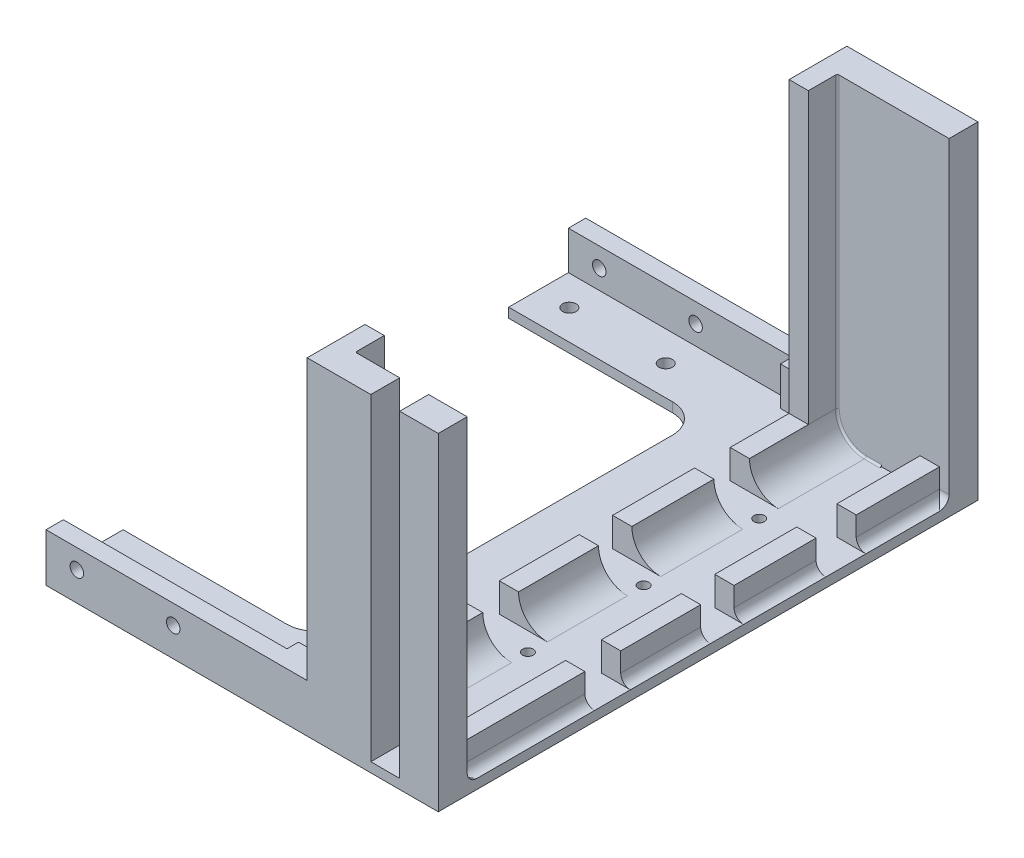
SolidWorks part; units mm, degrees
ref_plane "Front Plane" through (0, 0, 0) normal (0, 0, 1) x (1, 0, 0)
ref_plane "Top Plane" through (0, 0, 0) normal (0, 1, 0) x (1, 0, 0)
ref_plane "Right Plane" through (0, 0, 0) normal (1, 0, 0) x (0, 0, -1)
sketch "profile" plane through (0, 0, 0) normal (0, 0, 1) x (1, 0, 0)
  line L0 (11.8803, 7.4874) -> (14.5, 7.4874)
  line L1 (-5.5, 6.9749) -> (-7.8749, 4.6)
  line L2 (-7.8749, 4.6) -> (-12.1251, 4.6)
  line L3 (-12.1251, 4.6) -> (-14.5, 6.9749)
  line L4 (-8.1197, 7.4874) -> (-5.5, 7.4874)
  line L5 (-14.5, 6.9749) -> (-15.0126, 7.4874)
  line L6 (14.5, 6.9749) -> (12.1251, 4.6)
  line L7 (12.1251, 4.6) -> (7.8749, 4.6)
  line L8 (7.8749, 4.6) -> (5.5, 6.9749)
  line L9 (-14.7464, 10.3536) -> (-5.2536, 10.3536)
  line L10 (-14.5, 7.4874) -> (-11.8803, 7.4874)
  line L11 (5.5, 7.4874) -> (8.5334, 7.4874)
  line L12 (5.6673, 10.3536) -> (14.7464, 10.3536)
  line L13 (-15.0126, 7.4874) -> (-14.5, 7.4874)
  line L14 (-5.5, 6.9749) -> (-4.9874, 7.4874)
  line L15 (-4.9874, 7.4874) -> (-5.5, 7.4874)
  line L16 (5.5, 6.9749) -> (4.9874, 7.4874)
  line L17 (4.9874, 7.4874) -> (5.5, 7.4874)
  line L18 (14.5, 6.9749) -> (15.0126, 7.4874)
  line L19 (15.0126, 7.4874) -> (14.5, 7.4874)
  line L20 (-12.7464, 8.3536) -> (-14.7464, 10.3536)
  line L21 (-5.2536, 10.3536) -> (-7.2536, 8.3536)
  line L22 (7.6673, 8.3536) -> (5.6673, 10.3536)
  line L23 (14.7464, 10.3536) -> (12.7464, 8.3536)
  line L24 (-12.7464, 8.3536) -> (-11.8803, 7.4874)
  line L25 (-7.2536, 8.3536) -> (-8.1197, 7.4874)
  line L26 (7.6673, 8.3536) -> (8.5334, 7.4874)
  line L27 (12.7464, 8.3536) -> (11.8803, 7.4874)
  line L28 (-14.7464, 10.3536) -> (-20, 10.3536)
  line L29 (-20, 10.3536) -> (-20, 15.3536)
  line L30 (-20, 15.3536) -> (20, 15.3536)
  line L31 (20, 15.3536) -> (20, 10.3536)
  line L32 (20, 10.3536) -> (14.7464, 10.3536)
  line L33 (-5.2536, 10.3536) -> (5.6673, 10.3536)
  point P0 (-10, 4.6)
  point P1 (10, 4.6)
  dimension "D1" = 4.2503
  dimension "D2" = 5.7536
  dimension "D3" = 15.7497
  dimension "D4" = 20
  dimension "D5" = 5
extrude "Boss-Extrude1" add sketch "profile" along normal blind 250 contours L9 L33 L12 L32 L31 L30 L29 L28 region at (0, 12.8536, 0)
extrude "Boss-Extrude2" add sketch "Sketch1<3>" along normal blind 50 separate body contours L25 L21 L9 L20 L24 L10 L13 L5 L3 L2 L1 L14 L15 L4 | L27 L23 L12 L22 L26 L11 L17 L16 L8 L7 L6 L18 L19 L0 region at (10.0959, 7.5838, 0) region at (-10, 7.6238, 0)
sketch "Sketch1<3>" plane through (0, 0, 0) normal (0, 0, 1) x (1, 0, 0) same geometry as "profile"
pattern_linear "LPattern1" count 4 spacing 60 along (0, 0, 1) of "Boss-Extrude2"
sketch "Sketch2" plane through (0, 10.3536, 0) normal (0, -1, 0) x (1, 0, 0)
  line L0 (10, 250) -> (10, 0) construction
  line L1 (-20, 250) -> (20, 250) construction
  line L2 (12.1251, 0) -> (7.8749, 0) construction
  line L3 (-10, 230) -> (-10, 0) construction
  line L4 (-7.8749, 230) -> (-12.1251, 230) construction
  line L5 (-7.8749, 0) -> (-12.1251, 0) construction
  line L6 (-7.8749, 180) -> (-7.8749, 170) construction
  line L7 (-7.8749, 180) -> (-12.1251, 180) construction
  circle A0 centre (-10, 175) radius 2.75
  circle A1 centre (10, 175) radius 2.75
  circle A2 centre (-10, 115) radius 2.75
  circle A3 centre (10, 115) radius 2.75
  circle A4 centre (-10, 55) radius 2.75
  circle A5 centre (10, 55) radius 2.75
  point P21 (-7.8749, 175)
  dimension "D1" = 5.5
  dimension "D2" = 3
extrude "Cut-Extrude1" cut sketch "Sketch2" against normal through all
sketch "upper_acrylic_supp" plane through (0, 15.3536, 0) normal (0, 1, 0) x (1, 0, 0)
  line L0 (-20, 0) -> (20, 0) construction
  line L1 (-20, -250) -> (-34.5, -250) construction
  line L2 (-20, -250) -> (-20, 0) construction
  line L3 (-20, 0) -> (-34.5, 0) construction
  line L4 (-34.5, -250) -> (-34.5, 0) construction
  line L6 (-34.5, -250) -> (-24.5, -250)
  line L7 (-34.5, -250) -> (-34.5, -183.9264)
  line L8 (-34.5, -183.9264) -> (-24.5, -183.9264)
  line L9 (-24.5, -250) -> (-24.5, -183.9264)
  line L10 (-34.5, -165.3527) -> (-24.5, -165.3527)
  line L11 (-34.5, -165.3527) -> (-34.5, -123.8775)
  line L12 (-34.5, -123.8775) -> (-24.5, -123.8775)
  line L13 (-24.5, -165.3527) -> (-24.5, -123.8775)
  line L14 (-34.5, -106.5661) -> (-24.5, -106.5661)
  line L15 (-34.5, -106.5661) -> (-34.5, -64.0089)
  line L16 (-34.5, -64.0089) -> (-24.5, -64.0089)
  line L17 (-24.5, -106.5661) -> (-24.5, -64.0089)
  line L18 (-34.5, -45.5583) -> (-24.5, -45.5583)
  line L19 (-34.5, -45.5583) -> (-34.5, 0)
  line L20 (-34.5, 0) -> (-24.5, 0)
  line L21 (-24.5, -45.5583) -> (-24.5, 0)
  line L22 (-20, -250) -> (-40, -250)
  line L23 (-20, -250) -> (-20, 0)
  line L24 (-20, 0) -> (-40, 0)
  line L25 (-40, -250) -> (-40, 0)
  line M21 (-20, 0) -> (-20, -250)
  dimension "D1" = 5.5
  dimension "D2" = 10
  dimension "D3" = 20
extrude "Boss-Extrude3" add sketch "upper_acrylic_supp" against normal blind 5 contours L25 L22 L24 L21 L18 L19 L17 L14 L15 L16 L13 L10 L11 L12 L9 L6 L7 L8 M21 | L14 L17 L16 L15 | L10 L13 L12 L11 | L6 L9 L8 L7 | L18 L21 L20 L19 region at (-29.5, 15.3536, 216.9632) region at (-30.3215, 15.3536, 123.2164) region at (-29.5, 15.3536, 22.7792) region at (-29.5, 15.3536, 144.6151) region at (-29.5, 15.3536, 85.2875)
extrude "Boss-Extrude4" add sketch "upper_acrylic_supp<3>" along normal blind 15 contours L6 L9 L8 L7 | L10 L13 L12 L11 | L14 L17 L16 L15 | L18 L21 L20 L19 region at (-29.5, 15.3536, 216.9632) region at (-29.5, 15.3536, 22.7792) region at (-29.5, 15.3536, 144.6151) region at (-29.5, 15.3536, 85.2875)
sketch "upper_acrylic_supp<3>" plane through (0, 15.3536, 0) normal (0, 1, 0) x (1, 0, 0) same geometry as "upper_acrylic_supp"
fillet "Fillet1" radius 15 4 edges at (-24.5, 15.3536, 22.7792) (-24.5, 15.3536, 85.2875) (-24.5, 15.3536, 144.6151) (-24.5, 15.3536, 216.9632)
sketch "Sketch4" plane through (0, 15.3536, 0) normal (0, 1, 0) x (1, 0, 0)
  line L0 (20, -250) -> (20, 0) construction
  line L1 (-40, -250) -> (20, -250)
  line L2 (-40, -250) -> (-40, -265)
  line L3 (-40, -265) -> (20, -265)
  line L4 (20, -250) -> (20, -265)
  line L5 (-40, 0) -> (20, 0)
  line L6 (-40, 0) -> (-40, 15)
  line L7 (-40, 15) -> (20, 15)
  line L8 (20, 0) -> (20, 15)
  line L10 (-34.5, -265) -> (-34.5, 15) construction
  dimension "D1" = 15
  dimension "D2" = 15
extrude "Boss-Extrude5" add sketch "Sketch4" along normal mid plane 10
extrude "Boss-Extrude6" add sketch "Sketch4<3>" along normal blind 60
sketch "Sketch4<3>" plane through (0, 15.3536, 0) normal (0, 1, 0) x (1, 0, 0) same geometry as "Sketch4"
sketch "Sketch5" plane through (0, 0, 250) normal (0, 0, -1) x (-1, 0, 0)
  line L0 (-20, 75.3536) -> (40, 75.3536) construction
  line L1 (40, 15.3536) -> (34.5, 15.3536)
  line L2 (40, 15.3536) -> (40, 75.3536)
  line L3 (40, 75.3536) -> (34.5, 75.3536)
  line L4 (34.5, 15.3536) -> (34.5, 75.3536)
  line L6 (34.5, 15.3536) -> (24.5, 15.3536)
  line L7 (34.5, 15.3536) -> (34.5, 75.3536)
  line L8 (34.5, 75.3536) -> (24.5, 75.3536)
  line L9 (24.5, 15.3536) -> (24.5, 75.3536)
  line M5 (40, 75.3536) -> (-20, 75.3536)
  line M9 (24.5, 30.3536) -> (34.5, 30.3536)
  dimension "D1" = 5.5
  dimension "D2" = 10
extrude "Boss-Extrude7" add sketch "Sketch5" along normal blind 15 contours L9 L4 M9 M5 region at (-29.5, 52.8536, 250)
extrude "Boss-Extrude8" add sketch "Sketch5<3>" against normal blind 15 from surface contours L9 L4 M9 M5 region at (-29.5, 52.8536, 250) starting at face at (-18.2633, 33.7152, 0)
sketch "Sketch5<3>" plane through (0, 0, 250) normal (0, 0, -1) x (-1, 0, 0) same geometry as "Sketch5"
fillet "Fillet2" radius 1 6 edges at (5.25, 15.3536, 0) (-20.1066, 19.747, 0) (5.25, 15.3536, 250) (-20.1066, 19.747, 250) (-24.5, 52.8536, 0) (-24.5, 52.8536, 250)
sketch "Sketch6" plane through (-40, 0, 0) normal (-1, 0, 0) x (0, 0, 1)
  line L1 (250, 15.3536) -> (256, 15.3536)
  line L2 (250, 15.3536) -> (250, 75.3536)
  line L3 (250, 75.3536) -> (256, 75.3536)
  line L4 (256, 15.3536) -> (256, 75.3536)
  line L6 (0, 15.3536) -> (-6, 15.3536)
  line L7 (0, 15.3536) -> (0, 75.3536)
  line L8 (0, 75.3536) -> (-6, 75.3536)
  line L9 (-6, 15.3536) -> (-6, 75.3536)
  dimension "D1" = 6
  dimension "D2" = 6
extrude "Cut-Extrude2" cut sketch "Sketch6" against normal blind 6
sketch "Sketch7" plane through (-40, 0, 0) normal (-1, 0, 0) x (0, 0, 1)
  line L8 (265, 75.3536) -> (256, 75.3536)
  line L9 (256, 75.3536) -> (256, 15.3536)
  line L10 (256, 15.3536) -> (-6, 15.3536)
  line L11 (-6, 15.3536) -> (-6, 75.3536)
  line L12 (-6, 75.3536) -> (-15, 75.3536)
  line L13 (-15, 75.3536) -> (-15, 10.3536)
  line L14 (-15, 10.3536) -> (265, 10.3536)
  line L15 (265, 10.3536) -> (265, 75.3536)
  line L16 (265, 75.3536) -> (256, 75.3536)
  line L17 (256, 75.3536) -> (256, 15.3536)
  line L18 (256, 15.3536) -> (-6, 15.3536)
  line L19 (-6, 15.3536) -> (-6, 75.3536)
  line L20 (-6, 75.3536) -> (-15, 75.3536)
  line L21 (-15, 75.3536) -> (-15, 10.3536)
  line L22 (-15, 10.3536) -> (265, 10.3536)
  line L23 (265, 10.3536) -> (265, 75.3536)
  dimension "D1" = 0
extrude "Boss-Extrude9" add sketch "Sketch7" along normal blind 30
sketch "Sketch8" plane through (-70, 0, 0) normal (-1, 0, 0) x (0, 0, 1)
  line L0 (-15, 10.3536) -> (265, 10.3536) construction
  line L1 (-44.3745, 35.3536) -> (289.2282, 35.3536)
  line L2 (-44.3745, 35.3536) -> (-44.3745, 94.3849)
  line L3 (-44.3745, 94.3849) -> (289.2282, 94.3849)
  line L4 (289.2282, 35.3536) -> (289.2282, 94.3849)
  dimension "D1" = 25
extrude "Cut-Extrude3" cut sketch "Sketch8" against normal blind 150
sketch "Sketch9" plane through (-34, 0, 0) normal (-1, 0, 0) x (0, 0, 1)
  line L4 (256, 15.3536) -> (256, 35.3536)
  line L5 (256, 35.3536) -> (250, 35.3536)
  line L6 (250, 35.3536) -> (250, 15.3536)
  line L7 (250, 15.3536) -> (256, 15.3536)
  line L8 (256, 15.3536) -> (256, 35.3536)
  line L9 (256, 35.3536) -> (250, 35.3536)
  line L10 (250, 35.3536) -> (250, 15.3536)
  line L11 (250, 15.3536) -> (256, 15.3536)
  line L12 (0, 35.3536) -> (-6, 35.3536)
  line L13 (-6, 35.3536) -> (-6, 15.3536)
  line L14 (-6, 15.3536) -> (0, 15.3536)
  line L15 (0, 15.3536) -> (0, 35.3536)
  line L16 (0, 35.3536) -> (-6, 35.3536)
  line L17 (-6, 35.3536) -> (-6, 15.3536)
  line L18 (-6, 15.3536) -> (0, 15.3536)
  line L19 (0, 15.3536) -> (0, 35.3536)
  dimension "D1" = 0
  dimension "D2" = 0
extrude "cloth_escape_gap" add sketch "Sketch9" along normal blind 20
sketch "Sketch11" plane through (-70, 0, 0) normal (-1, 0, 0) x (0, 0, 1)
  line L0 (256, 35.3536) -> (256, 15.3536) construction
  line L1 (-15, 35.3536) -> (-6, 35.3536)
  line L2 (-15, 35.3536) -> (-15, 15.3536)
  line L3 (-15, 15.3536) -> (-6, 15.3536)
  line L4 (-6, 35.3536) -> (-6, 15.3536)
  line L5 (265, 35.3536) -> (256, 35.3536)
  line L6 (265, 35.3536) -> (265, 15.3536)
  line L7 (265, 15.3536) -> (256, 15.3536)
  line L8 (256, 35.3536) -> (256, 15.3536)
  line L9 (256, 15.3536) -> (256, 35.3536) construction
extrude "Boss-Extrude11" add sketch "Sketch11" along normal blind 100
sketch "Sketch12" plane through (0, 10.3536, 0) normal (0, -1, 0) x (1, 0, 0)
  line L0 (-70, -15) -> (-170, -10.5)
  line L1 (-170, -15) -> (-170, -6) construction
  line L2 (-170, -10.5) -> (-170, -15)
  line L3 (-170, -15) -> (-70, -15) construction
  line L4 (-170, -15) -> (-70, -15)
  line L5 (-70, 265) -> (-170, 260.5)
  line L6 (-170, 256) -> (-170, 265) construction
  line L7 (-170, 260.5) -> (-170, 265)
  line L8 (-170, 265) -> (-70, 265)
extrude "Cut-Extrude4" cut sketch "Sketch12" against normal blind 68 contours L8 L7 L5 | L0 L2 L4 region at (-136.6667, 10.3536, 263.5)
sketch "Sketch13" plane through (-70, 0, 0) normal (-1, 0, 0) x (0, 0, 1)
  line L0 (256, 15.3536) -> (265, 15.3536) construction
  line L1 (-15, 10.3536) -> (25, 10.3536)
  line L2 (-15, 10.3536) -> (-15, 15.3536)
  line L3 (-15, 15.3536) -> (25, 15.3536)
  line L4 (25, 10.3536) -> (25, 15.3536)
  line L5 (265, 10.3536) -> (225, 10.3536)
  line L6 (265, 10.3536) -> (265, 15.3536)
  line L7 (265, 15.3536) -> (225, 15.3536)
  line L8 (225, 10.3536) -> (225, 15.3536)
  line L9 (256, 15.3536) -> (-6, 15.3536) construction
  dimension "D1" = 40
  dimension "D2" = 40
extrude "Boss-Extrude13" add sketch "Sketch13" along normal blind 100
sketch "Sketch14" plane through (0, 15.3536, 0) normal (0, 1, 0) x (1, 0, 0)
  line L3 (-70, -265) -> (-170, -260.5)
  line L4 (-170, -260.5) -> (-170, -265)
  line L5 (-170, -265) -> (-70, -265)
  line L6 (-70, -265) -> (-170, -260.5)
  line L7 (-170, -260.5) -> (-170, -265)
  line L8 (-170, -265) -> (-70, -265)
  line L9 (-170, 15) -> (-170, 10.5)
  line L10 (-170, 10.5) -> (-70, 15)
  line L11 (-70, 15) -> (-170, 15)
  line L12 (-170, 15) -> (-170, 10.5)
  line L13 (-170, 10.5) -> (-70, 15)
  line L14 (-70, 15) -> (-170, 15)
  dimension "D1" = 0
  dimension "D2" = 0
extrude "Cut-Extrude5" cut sketch "Sketch14" against normal blind 100
fillet "Fillet3" radius 15 2 edges at (-70, 12.8536, 25) (-70, 12.8536, 225)
sketch "Sketch16" plane through (0, 15.3536, 0) normal (0, 1, 0) x (1, 0, 0)
  line L0 (20, -1) -> (-9.5, -1) construction
  line L1 (-34.5, -235) -> (18.5, -235) construction
  line L2 (-34.5, -235) -> (-34.5, -1) construction
  line L3 (-34.5, -1) -> (18.5, -1) construction
  line L4 (18.5, -235) -> (18.5, -1) construction
  line L5 (20, -265) -> (-70, -265) construction
  line L6 (18.5, -265) -> (33.5, -265)
  line L7 (18.5, -265) -> (18.5, 15)
  line L8 (18.5, 15) -> (33.5, 15)
  line L9 (33.5, -265) -> (33.5, 15)
  line L10 (-70, 15) -> (20, 15) construction
  line L11 (18.5, -250) -> (33.5, -250)
  line L12 (18.5, 0) -> (33.5, 0)
  line L13 (-23.5, -250) -> (20, -250) construction
  line L14 (-9.5, 0) -> (20, 0) construction
  line L15 (18.5, -250) -> (28.5, -250)
  line L16 (28.5, -250) -> (28.5, -183.9264)
  line L17 (28.5, 0) -> (18.5, 0)
  line L18 (18.5, -183.9264) -> (28.5, -183.9264)
  line L19 (18.5, -165.3527) -> (28.5, -165.3527)
  line L20 (18.5, -123.8775) -> (28.5, -123.8775)
  line L21 (18.5, -106.5661) -> (28.5, -106.5661)
  line L22 (18.5, -64.0089) -> (28.5, -64.0089)
  line L23 (18.5, -43.1778) -> (28.5, -43.1778)
  line L24 (-34.5, -165.3527) -> (-9.5, -165.3527) construction
  line L25 (-34.5, -183.9264) -> (-9.5, -183.9264) construction
  line L26 (-34.5, -106.5661) -> (-9.5, -106.5661) construction
  line L27 (-34.5, -123.8775) -> (-9.5, -123.8775) construction
  line L28 (-9.5, -64.0089) -> (-24.5, -64.0089) construction
  line L30 (28.5, -165.3527) -> (28.5, -123.8775)
  line L31 (28.5, -106.5661) -> (28.5, -64.0089)
  line L32 (28.5, -43.1778) -> (28.5, 0)
  line M38 (-9.5, -249) -> (20, -249)
  line M39 (20, -249) -> (20, -1)
  line M40 (20, -1) -> (-9.5, -1)
  dimension "D1" = 53
  dimension "D2" = 15
  dimension "D3" = 10
extrude "Boss-Extrude14" add sketch "Sketch16" along direction (0, -1, 0) on the side of the normal up to surface (20 mm away) from surface contours L7 L12 L9 L8 | L11 L7 L6 L9 region at (26, 15.3536, 257.5) region at (26, 15.3536, -7.5) up to face at (-51.6423, 35.3536, 251.8089) starting at face at (-10, 10.3536, 25)
extrude "Cut-Extrude6" cut sketch "Sketch16<5>" against normal blind 10 and the other way blind 30 contours L11 L7 L6 L9 | L32 L23 L22 L31 L21 L20 L30 L19 L18 L16 L11 L9 L12 M39 | L19 L30 L20 M39 | L21 L31 L22 M39 | L23 L32 L12 L7 M40 M39 | L7 L12 L9 L8 | L7 L23 M39 M40 | L23 L7 L22 M39 | L22 L7 L21 M39 | L21 L7 L20 M39 | L20 L7 L19 M39 | L19 L7 L18 M39 | L18 L7 M38 M39 | L18 L7 L11 L16 M39 M38 region at (26, 15.3536, 257.5) region at (24.2367, 15.3536, 217.0499) region at (29.1213, 15.3536, 121.3942) region at (19.25, 15.3536, 216.4632) region at (26, 15.3536, -7.5) region at (19.25, 15.3536, 174.6396) region at (24.2296, 15.3536, 21.5031) region at (19.25, 15.3536, 144.6151) region at (19.25, 15.3536, 115.2218) region at (24.25, 15.3536, 144.6151) region at (19.25, 15.3536, 22.0889) region at (19.25, 15.3536, 53.5934) region at (19.25, 15.3536, 85.2875) region at (24.25, 15.3536, 85.2875)
sketch "Sketch16<5>" plane through (0, 15.3536, 0) normal (0, 1, 0) x (1, 0, 0) same geometry as "Sketch16"
extrude "Boss-Extrude15" add sketch "Sketch16<6>" against normal up to surface (5 mm away) contours L32 L23 L22 L31 L21 L20 L30 L19 L18 L16 L11 L9 L12 M39 | L18 L7 L11 L16 M39 M38 | L11 L7 L6 L9 | L19 L30 L20 M39 | L21 L31 L22 M39 | L23 L32 L12 L7 M40 M39 | L7 L12 L9 L8 | L7 L23 M39 M40 | L23 L7 L22 M39 | L22 L7 L21 M39 | L21 L7 L20 M39 | L20 L7 L19 M39 | L19 L7 L18 M39 | L18 L7 M38 M39 region at (26, 15.3536, 257.5) region at (24.2367, 15.3536, 217.0499) region at (29.1213, 15.3536, 121.3942) region at (19.25, 15.3536, 216.4632) region at (26, 15.3536, -7.5) region at (19.25, 15.3536, 174.6396) region at (24.2296, 15.3536, 21.5031) region at (19.25, 15.3536, 144.6151) region at (19.25, 15.3536, 115.2218) region at (24.25, 15.3536, 144.6151) region at (19.25, 15.3536, 22.0889) region at (19.25, 15.3536, 53.5934) region at (19.25, 15.3536, 85.2875) region at (24.25, 15.3536, 85.2875) up to face at (-90.5656, 10.3536, 125)
sketch "Sketch16<6>" plane through (0, 15.3536, 0) normal (0, 1, 0) x (1, 0, 0) same geometry as "Sketch16"
extrude "Boss-Extrude16" add sketch "Sketch16<7>" along normal up to surface (20 mm away) contours L11 L7 L6 L9 | L7 L12 L9 L8 region at (26, 15.3536, 257.5) region at (26, 15.3536, -7.5) up to face at (-51.8923, 35.3536, 251.8089)
sketch "Sketch16<7>" plane through (0, 15.3536, 0) normal (0, 1, 0) x (1, 0, 0) same geometry as "Sketch16"
extrude "Boss-Extrude17" add sketch "Sketch16<8>" along normal up to surface (15 mm away) contours L18 L7 L11 L16 M39 M38 | L19 L30 L20 M39 | L21 L31 L22 M39 | L23 L32 L12 L7 M40 M39 | L7 L23 M39 M40 | L22 L7 L21 M39 | L20 L7 L19 M39 | L18 L7 M38 M39 region at (24.2367, 15.3536, 217.0499) region at (19.25, 15.3536, 216.4632) region at (24.2296, 15.3536, 21.5031) region at (19.25, 15.3536, 144.6151) region at (24.25, 15.3536, 144.6151) region at (19.25, 15.3536, 22.0889) region at (19.25, 15.3536, 85.2875) region at (24.25, 15.3536, 85.2875) up to face at (-29.5, 30.3536, 209.4632)
sketch "Sketch16<8>" plane through (0, 15.3536, 0) normal (0, 1, 0) x (1, 0, 0) same geometry as "Sketch16"
extrude "Boss-Extrude18" add sketch "Sketch14<2>" along normal up to surface (20 mm away) and the other way up to surface (5 mm away) up to face at (-49.3923, 35.3536, -1.8089) other way up to face at (-88.0656, 10.3536, 125)
sketch "Sketch14<2>" plane through (0, 15.3536, 0) normal (0, 1, 0) x (1, 0, 0) same geometry as "Sketch14"
fillet "Fillet4" radius 5 6 edges at (31, 15.3536, 250) (31, 15.3536, 0) (28.5, 15.3536, 21.5889) (28.5, 15.3536, 85.2875) (28.5, 15.3536, 144.6151) (28.5, 15.3536, 216.9632)
sketch "Sketch18" plane through (0, 35.3536, 0) normal (0, 1, 0) x (1, 0, 0)
  line L2 (-34.5, -250) -> (-34.5, -265)
  line L3 (-34.5, 15) -> (-34.5, 0)
  line L12 (-23.5, 0) -> (33.5, 0)
  line L13 (33.5, 0) -> (33.5, 15)
  line L14 (33.5, 15) -> (-170, 15)
  line L15 (-170, 15) -> (-170, 6)
  line L30 (-170, 6) -> (-54, 6)
  line L32 (-54, 6) -> (-54, 0)
  line L38 (-54, 0) -> (-34.5, 0)
  line L39 (-34.5, 0) -> (-34.5, -15)
  line L50 (-34.5, -15) -> (-24.5, -15)
  line L51 (-24.5, -15) -> (-24.5, -1)
  line L52 (-23.5, 0) -> (33.5, 0)
  line L53 (33.5, 0) -> (33.5, 15)
  line L54 (33.5, 15) -> (-34.5, 15)
  line L59 (-34.5, 0) -> (-34.5, -15)
  line L60 (-34.5, -15) -> (-24.5, -15)
  line L61 (-24.5, -15) -> (-24.5, -1)
  line L62 (-170, -265) -> (33.5, -265)
  line L63 (33.5, -265) -> (33.5, -250)
  line L64 (33.5, -250) -> (-23.5, -250)
  line L65 (-24.5, -249) -> (-24.5, -235)
  line L66 (-24.5, -235) -> (-34.5, -235)
  line L67 (-34.5, -235) -> (-34.5, -250)
  line L68 (-34.5, -250) -> (-54, -250)
  line L69 (-54, -250) -> (-54, -256)
  line L70 (-54, -256) -> (-170, -256)
  line L71 (-170, -256) -> (-170, -265)
  line L72 (-34.5, -265) -> (33.5, -265)
  line L73 (33.5, -265) -> (33.5, -250)
  line L74 (33.5, -250) -> (-23.5, -250)
  line L75 (-24.5, -249) -> (-24.5, -235)
  line L76 (-24.5, -235) -> (-34.5, -235)
  line L77 (-34.5, -235) -> (-34.5, -250)
  arc A5 (-23.5, 0) -> (-24.5, -1) centre (-23.5, -1) ccw
  arc A6 (-23.5, 0) -> (-24.5, -1) centre (-23.5, -1) ccw
  arc A7 (-24.5, -249) -> (-23.5, -250) centre (-23.5, -249) ccw
  arc A8 (-24.5, -249) -> (-23.5, -250) centre (-23.5, -249) ccw
  dimension "D1" = 0
  dimension "D2" = 0
extrude "Boss-Extrude21" add sketch "Sketch18" along normal blind 170 from surface starting at face at (-91.6787, 10.3536, 125)
sketch "Sketch19" plane through (0, 15.3536, 0) normal (0, 1, 0) x (1, 0, 0)
  line L0 (-170, -25) -> (-170, 6) construction
  line L1 (-70, -125) -> (-196.5165, -125) construction
  line L2 (-70, -210) -> (-70, -40) construction
  circle A0 centre (-154, -9.5) radius 3.5
  circle A1 centre (-104, -9.5) radius 3.5
  circle A2 centre (-104, -240.5) radius 3.5
  circle A3 centre (-154, -240.5) radius 3.5
  point P6 (-170, -9.5)
  dimension "D1" = 7
  dimension "D2" = 50
  dimension "D3" = 50
extrude "Cut-Extrude7" cut sketch "Sketch19" against normal blind 10
sketch "Sketch20" plane through (0, 0, 256) normal (0, 0, -1) x (-1, 0, 0)
  line L4 (34.5, 35.3536) -> (34.5, 15.3536)
  line L5 (34.5, 15.3536) -> (54, 15.3536)
  line L6 (54, 15.3536) -> (54, 35.3536)
  line L7 (54, 35.3536) -> (34.5, 35.3536)
  line L8 (34.5, 35.3536) -> (34.5, 15.3536)
  line L9 (34.5, 15.3536) -> (54, 15.3536)
  line L10 (54, 15.3536) -> (54, 35.3536)
  line L11 (54, 35.3536) -> (34.5, 35.3536)
  circle A0 centre (104, 25.3536) radius 3.5
  circle A1 centre (154, 25.3536) radius 3.5
  point P8 (54, 25.3536)
  dimension "D3" = 7
  dimension "D2" = 50
  dimension "D4" = 50
  dimension "D1" = 0
extrude "Cut-Extrude8" cut sketch "Sketch20" against normal blind 10 and the other way blind 355 contours A0 | A1 region at (-104, 25.3536, 256) region at (-154, 25.3536, 256)
sketch "Sketch21" plane through (0, 0, 0) normal (0, 0, 1) x (1, 0, 0)
  line L1 (13.5, 15.3536) -> (-1.5, 15.3536)
  line L2 (13.5, 15.3536) -> (13.5, 212.8546)
  line L3 (13.5, 212.8546) -> (-1.5, 212.8546)
  line L4 (-1.5, 15.3536) -> (-1.5, 212.8546)
  line L6 (18.5, 15.3536) -> (-9.5, 15.3536) construction
  line L7 (18.5, 30.3536) -> (18.5, 16.3536) construction
  dimension "D1" = 15
  dimension "D2" = 5
extrude "Cut-Extrude9" cut sketch "Sketch21" along normal blind 340
